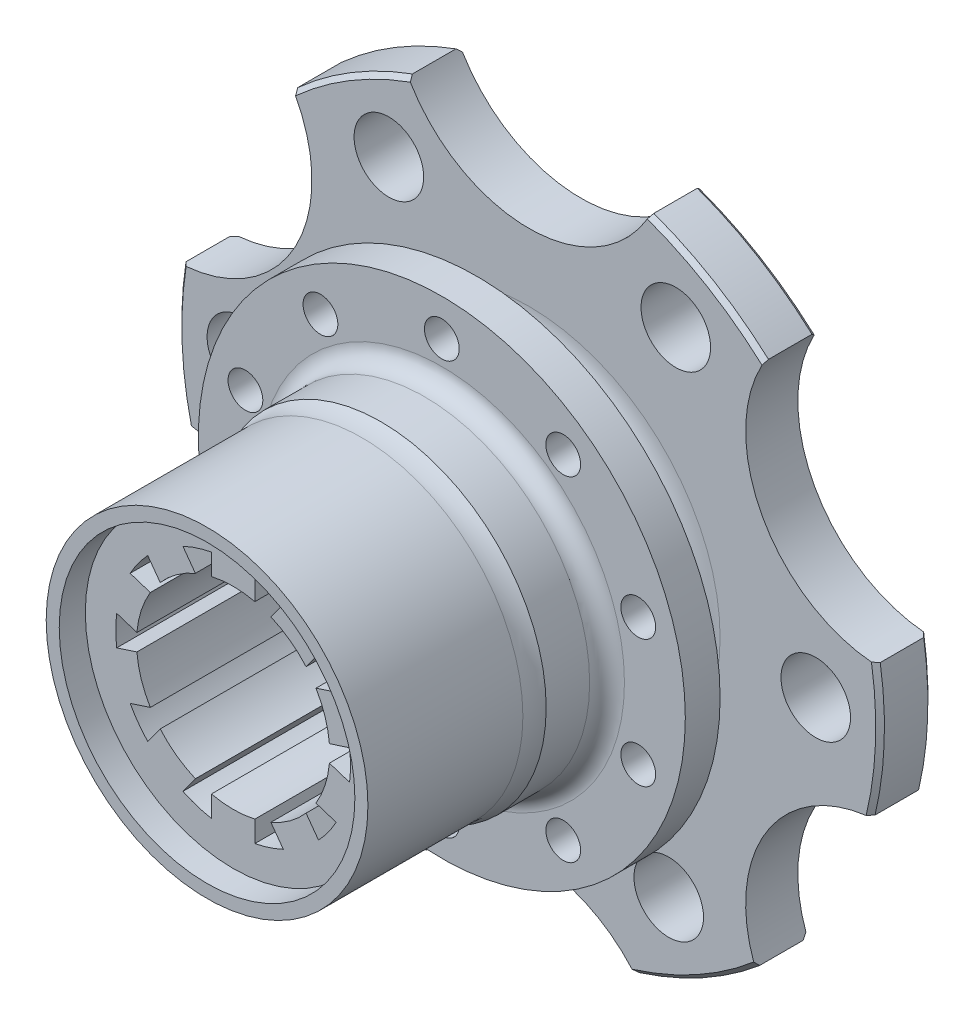
SolidWorks part; units mm, degrees
material "Aluminum Bronze"
ref_plane "Front Plane" through (0, 0, 0) normal (0, 0, 1) x (1, 0, 0)
ref_plane "Top Plane" through (0, 0, 0) normal (0, 1, 0) x (1, 0, 0)
ref_plane "Right Plane" through (0, 0, 0) normal (1, 0, 0) x (0, 0, -1)
sketch "Sketch1" plane through (0, 0, 0) normal (0, 0, 1) x (1, 0, 0)
  circle A0 centre (0, 0) radius 40.4
  dimension "D1" = 80.8
extrude "Boss-Extrude1" add sketch "Sketch1" along normal mid plane 6
sketch "Sketch2" plane through (0, 0, 0) normal (0, 0, 1) x (1, 0, 0)
  line L0 (-30.296, 68.8104) -> (30.296, 68.8104)
  line L1 (0, 82.241) -> (0, -71.8262) construction
  line L2 (-30.296, 68.8104) -> (-14, 38.162)
  line L3 (14, 38.162) -> (30.296, 68.8104)
  circle A0 centre (0, 45.606) radius 15.856
  point P2 (0, 68.8104)
  point P10 (0, 29.75)
  dimension "D1" = 28
  dimension "D3" = 29.75
  dimension "D2" = 14
extrude "Cut-Extrude1" cut sketch "Sketch2" against normal through all both and the other way through all contours A0 L1 | L1 A0 | L0 L1 A0 L3 | L1 L0 L2 A0
pattern_circular "CirPattern1" count 6 over 360 about axis through (0, -1.4986, 0) along (0, 0, 1) of "Cut-Extrude1"
ref_plane "Plane1" through (0, 0, 3) normal (0, 0, 1) x (1, 0, 0)
sketch "Sketch3" plane through (0, 0, 3) normal (0, 0, 1) x (1, 0, 0)
  circle A0 centre (16.9052, 28.341) radius 4
  circle A1 centre (0, 0) radius 33 construction
  circle A2 centre (32.9967, -0.4698) radius 4
  circle A3 centre (16.0915, -28.8108) radius 4
  circle A4 centre (-16.9052, -28.341) radius 4
  circle A5 centre (-32.9967, 0.4698) radius 4
  circle A6 centre (-16.0915, 28.8108) radius 4
  point P17 (0, 0)
  dimension "D1" = 66
  dimension "D3" = 8
  dimension "D2" = 6
extrude "Cut-Extrude2" cut sketch "Sketch3" against normal through all
ref_plane "Plane2" through (0, 0, -3) normal (0, 0, -1) x (-1, 0, 0)
sketch "Sketch4" plane through (0, 0, -3) normal (0, 0, -1) x (-1, 0, 0)
  circle A0 centre (0, 0) radius 17
  dimension "D1" = 34
extrude "Boss-Extrude2" add sketch "Sketch4" against normal blind 40
ref_plane "Plane3" through (0, 0, 37) normal (0, 0, 1) x (1, 0, 0)
sketch "Sketch5" plane through (0, 0, 37) normal (0, 0, 1) x (1, 0, 0)
  circle A0 centre (0, 0) radius 11.1125
  dimension "D1" = 22.225
extrude "Cut-Extrude3" cut sketch "Sketch5" against normal through all both and the other way through all
fillet "Fillet1" radius 5 1 edges at (17, 0, 3)
ref_plane "Plane4" through (0, 0, 9) normal (0, 0, 1) x (1, 0, 0)
sketch "Sketch6" plane through (0, 0, 9) normal (0, 0, 1) x (1, 0, 0)
  circle A0 centre (0, 0) radius 17
  circle A1 centre (0, 0) radius 28
  dimension "D1" = 34
  dimension "D2" = 56
extrude "Boss-Extrude3" add sketch "Sketch6" along normal blind 4
ref_plane "Plane5" through (0, 0, 13) normal (0, 0, 1) x (1, 0, 0)
sketch "Sketch7" plane through (0, 0, 13) normal (0, 0, 1) x (1, 0, 0)
  circle A0 centre (0, 0) radius 17
  circle A1 centre (0, 0) radius 19
  dimension "D1" = 2
  dimension "D2" = 34
extrude "Boss-Extrude4" add sketch "Sketch7" along normal blind 7
ref_plane "Plane6" through (0, 0, 20) normal (0, 0, 1) x (1, 0, 0)
sketch "Sketch8" plane through (0, 0, 20) normal (0, 0, 1) x (1, 0, 0)
  circle A0 centre (0, 0) radius 17
  dimension "D1" = 34
extrude "Extrude-Thin1" add sketch "Sketch8" along normal blind 20 thin
sketch "Sketch9" plane through (0, 0, 13) normal (0, 0, 1) x (1, 0, 0)
  circle A0 centre (0, 23.75) radius 2
  circle A1 centre (0, 0) radius 23.75 construction
  circle A2 centre (13.9599, 19.2142) radius 2
  circle A3 centre (22.5876, 7.3392) radius 2
  circle A4 centre (22.5876, -7.3392) radius 2
  circle A5 centre (13.9599, -19.2142) radius 2
  circle A6 centre (0, -23.75) radius 2
  circle A7 centre (-13.9599, -19.2142) radius 2
  circle A8 centre (-22.5876, -7.3392) radius 2
  circle A9 centre (-22.5876, 7.3392) radius 2
  circle A10 centre (-13.9599, 19.2142) radius 2
  point P25 (0, 0)
  dimension "D1" = 47.5
  dimension "D2" = 4
  dimension "D3" = 10
extrude "Cut-Extrude4" cut sketch "Sketch9" against normal up to next
fillet "Fillet2" radius 5 1 edges at (18.5, 0, 20)
fillet "Fillet3" radius 2 1 edges at (19, 0, 13)
chamfer "Chamfer1" distance 0.5 angle 45 12 edges at (19.513, -35.3752, -3) (-19.513, -35.3752, -3) (-40.3703, -1.5494, -3) (-20.8562, 34.6003, -3) (20.8562, 34.6003, -3) (40.3703, -1.5494, -3) (19.513, -35.3752, 3) (40.3703, -1.5494, 3) (-19.513, -35.3752, 3) (-40.3703, -1.5494, 3) (-20.8562, 34.6003, 3) (20.8562, 34.6003, 3)
chamfer "Chamfer2" distance 4 angle 45 1 edges at (11.1125, 0, -3)
ref_plane "Plane7" through (0, 0, 37) normal (0, 0, 1) x (1, 0, 0)
sketch "Sketch10" plane through (0, 0, 37) normal (0, 0, 1) x (1, 0, 0)
  line L0 (0, 13.5) -> (0, 11.1125)
  line L1 (-2.5, 13.2665) -> (-2.5, 10.8276)
  line L2 (2.5, 13.2665) -> (2.5, 10.8276)
  line L3 (2.5, 15.4656) -> (2.5, 9.3012) construction
  line L4 (0, 15.4656) -> (0, 9.3012) construction
  line L5 (-2.5, 15.4656) -> (-2.5, 9.3012) construction
  line L6 (5.7753, 12.2023) -> (4.3418, 10.2292)
  line L7 (7.9351, 10.9217) -> (6.5318, 8.9902)
  line L8 (9.8204, 9.2634) -> (8.3869, 7.2903)
  line L9 (11.8446, 6.4772) -> (9.5251, 5.7236)
  line L10 (12.8393, 4.1717) -> (10.5686, 3.434)
  line L11 (13.3897, 1.7219) -> (11.0702, 0.9683)
  line L12 (13.3897, -1.7219) -> (11.0702, -0.9683)
  line L13 (12.8393, -4.1717) -> (10.5686, -3.434)
  line L14 (11.8446, -6.4772) -> (9.5251, -5.7236)
  line L15 (9.8204, -9.2634) -> (8.3869, -7.2903)
  line L16 (7.9351, -10.9217) -> (6.5318, -8.9902)
  line L17 (5.7753, -12.2023) -> (4.3418, -10.2292)
  line L18 (2.5, -13.2665) -> (2.5, -10.8276)
  line L19 (0, -13.5) -> (0, -11.1125)
  line L20 (-2.5, -13.2665) -> (-2.5, -10.8276)
  line L21 (-5.7753, -12.2023) -> (-4.3418, -10.2292)
  line L22 (-7.9351, -10.9217) -> (-6.5318, -8.9902)
  line L23 (-9.8204, -9.2634) -> (-8.3869, -7.2903)
  line L24 (-11.8446, -6.4772) -> (-9.5251, -5.7236)
  line L25 (-12.8393, -4.1717) -> (-10.5686, -3.434)
  line L26 (-13.3897, -1.7219) -> (-11.0702, -0.9683)
  line L27 (-13.3897, 1.7219) -> (-11.0702, 0.9683)
  line L28 (-12.8393, 4.1717) -> (-10.5686, 3.434)
  line L29 (-11.8446, 6.4772) -> (-9.5251, 5.7236)
  line L30 (-9.8204, 9.2634) -> (-8.3869, 7.2903)
  line L31 (-7.9351, 10.9217) -> (-6.5318, 8.9902)
  line L32 (-5.7753, 12.2023) -> (-4.3418, 10.2292)
  circle A0 centre (0, 0) radius 13.5
  circle A1 centre (0, 0) radius 11.1125
  point P73 (0, 0)
  dimension "D1" = 27
  dimension "D2" = 22.225
  dimension "D3" = 2.5
  dimension "D4" = 2.5
  dimension "D5" = 10
extrude "Cut-Extrude6" cut sketch "Sketch10" against normal through all both and the other way through all contours A1 L1 A0 L32 | A1 L6 A0 L2 | A1 L30 A0 L29 | A1 L27 A0 L26 | A1 L24 A0 L23 | A1 L21 A0 L20 | A1 L18 A0 L17 | A1 L15 A0 L14 | A1 L12 A0 L11 | A1 L9 A0 L8
